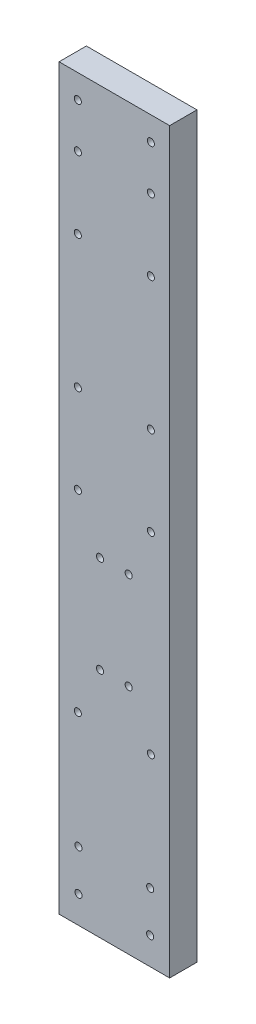
SolidWorks part; units mm, degrees
ref_plane "Front Plane" through (0, 0, 0) normal (0, 0, 1) x (1, 0, 0)
ref_plane "Top Plane" through (0, 0, 0) normal (0, 1, 0) x (1, 0, 0)
ref_plane "Right Plane" through (0, 0, 0) normal (1, 0, 0) x (0, 0, -1)
sketch "Sketch1" plane through (0, 0, 0) normal (0, 0, 1) x (1, 0, 0)
  line L0 (16.2, 0) -> (16.2, 108.14)
  line L1 (16.2, 108.14) -> (0, 108.14)
  line L2 (0, 108.14) -> (0, 0)
  line L3 (0, 0) -> (16.2, 0)
  line L4 (16.2, 57.71) -> (0, 57.71) construction
  line L5 (0, 12.5) -> (16.2, 12.5) construction
  line L6 (0, 24.5) -> (16.2, 24.5) construction
  line L7 (0, 90.16) -> (16.2, 90.16) construction
  line L8 (0, 65.71) -> (16.2, 65.71) construction
  line L9 (8.1, 108.14) -> (8.1, 96.16) construction
  line L11 (0, 96.16) -> (16.2, 96.16) construction
  circle A0 centre (13.45, 55.21) radius 0.52
  circle A1 centre (10.2, 48.21) radius 0.52
  circle A2 centre (13.45, 104.66) radius 0.52
  circle A3 centre (2.75, 98.16) radius 0.52
  circle A4 centre (6, 48.21) radius 0.52
  circle A5 centre (2.75, 27) radius 0.52
  circle A6 centre (2.75, 87.66) radius 0.52
  circle A7 centre (2.75, 55.21) radius 0.52
  circle A8 centre (13.45, 87.66) radius 0.52
  circle A9 centre (13.45, 98.16) radius 0.52
  circle A28 centre (13.45, 68.21) radius 0.52
  circle A29 centre (6, 34) radius 0.52
  circle A32 centre (2.75, 104.66) radius 0.52
  circle A33 centre (10.2, 34) radius 0.52
  circle A34 centre (2.75, 68.21) radius 0.52
  circle A35 centre (13.45, 27) radius 0.52
  circle A36 centre (2.85, 10) radius 0.52
  circle A37 centre (13.35, 10) radius 0.52
  circle A38 centre (13.35, 4) radius 0.52
  circle A39 centre (2.85, 4) radius 0.52
  dimension "D1" = 4
  dimension "D2" = 4
  dimension "D3" = 2.85
  dimension "D4" = 2.85
  dimension "D5" = 16.2
  dimension "D6" = 6
  dimension "D7" = 6
  dimension "D8" = 2.85
  dimension "D9" = 2.85
  dimension "D10" = 2.5
  dimension "D11" = 12
  dimension "D12" = 33.21
  dimension "D13" = 2.5
  dimension "D14" = 2.5
  dimension "D15" = 2.75
  dimension "D16" = 2.75
  dimension "D17" = 2.5
  dimension "D18" = 2.5
  dimension "D19" = 2.75
  dimension "D20" = 2.75
  dimension "D21" = 9.5
  dimension "D22" = 6
  dimension "D23" = 9.5
  dimension "D24" = 6
  dimension "D25" = 9.5
  dimension "D26" = 9.5
  dimension "D27" = 6
  dimension "D28" = 6
  dimension "D29" = 8
  dimension "D30" = 24.45
  dimension "D31" = 2.5
  dimension "D32" = 2.5
  dimension "D33" = 2.75
  dimension "D34" = 2.75
  dimension "D35" = 6
  dimension "D36" = 2.75
  dimension "D37" = 2
  dimension "D38" = 2.75
  dimension "D39" = 8.5
  dimension "D40" = 11.98
  dimension "D41" = 2.5
  dimension "D42" = 2.5
  dimension "D43" = 2.75
  dimension "D44" = 2.75
extrude "Boss-Extrude1" add sketch "Sketch1" along normal blind 4
equation "\"D12@Sketch1\"= \"HL@parametersSketch@prostheticParameters.SLDPRT\" * 0.266 - 12 - 4 'Middle PIP Length"
equation "\"D30@Sketch1\"= \"HL@parametersSketch@prostheticParameters.SLDPRT\" * 0.17 - 4 - 3'Middle MIP Length"
equation "\"D5@Sketch1\"= \"fingerWidth@parametersSketch@prostheticParameters.SLDPRT\" 'Middle Width"
equation "\"D40@Sketch1\"= \"HL@parametersSketch@prostheticParameters.SLDPRT\" * 0.108 - 3 - 5'Middle DIP Length"
